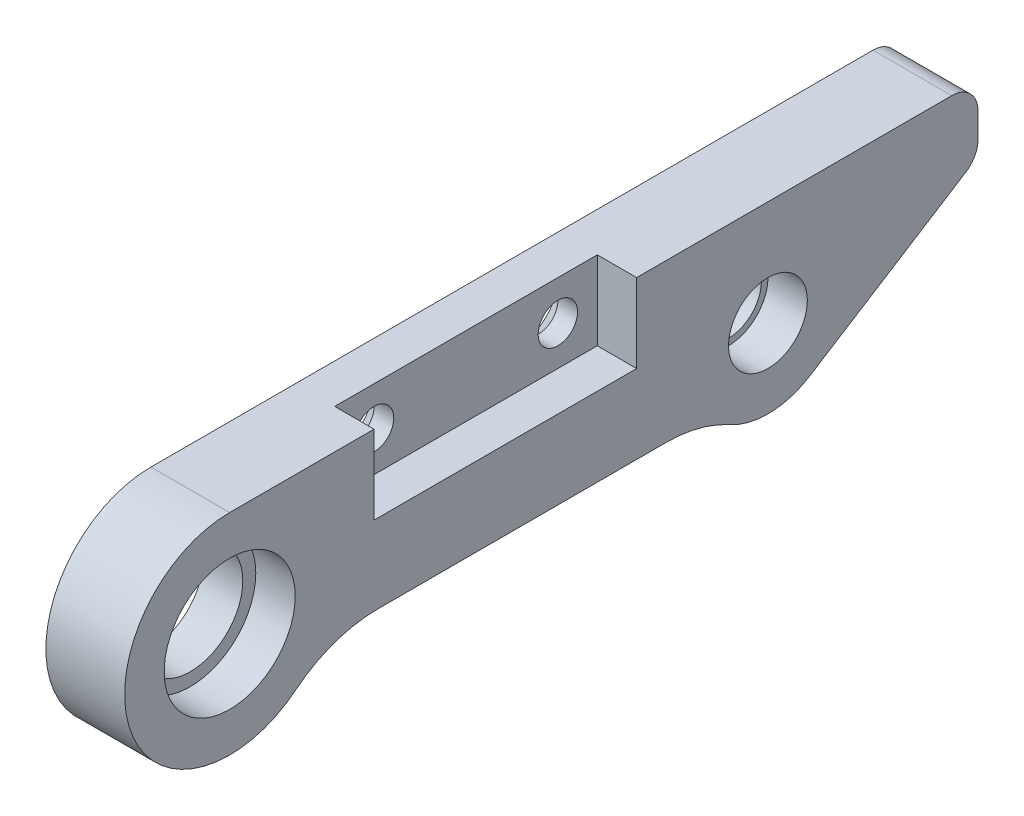
SolidWorks part; units mm, degrees
material "1060 Alloy"
ref_plane "Front Plane" through (0, 0, 0) normal (0, 0, 1) x (1, 0, 0)
ref_plane "Top Plane" through (0, 0, 0) normal (0, 1, 0) x (1, 0, 0)
ref_plane "Right Plane" through (0, 0, 0) normal (1, 0, 0) x (0, 0, -1)
sketch "Sketch27" plane through (0, 0, 0) normal (1, 0, 0) x (0, 0, -1)
  line L2 (9, 50) -> (66, 50)
  line L3 (9, 42) -> (30.9317, 42) construction
  line L4 (30.9317, 42) -> (30.9317, 54) construction
  line L6 (9, 34) -> (48.5644, 34)
  line L7 (30.9317, 54) -> (9, 42) construction
  line L8 (0, 0) -> (60, 0) construction
  line L9 (0, 0) -> (0, 58) construction
  line L10 (0, 58) -> (60, 58) construction
  line L11 (60, 0) -> (60, 58) construction
  line L12 (66, 50) -> (66, 45)
  line L13 (48.5644, 34) -> (66, 45)
  arc A0 (9, 50) -> (9, 34) centre (9, 42) ccw
  circle A1 centre (50, 42) radius 6 construction
  circle A3 centre (9, 42) radius 5.6 construction
  circle A5 centre (9, 42) radius 4
  circle A6 centre (50, 42) radius 2.5
  dimension "D9" = 12
  dimension "D10" = 5
  dimension "D12" = 8
  dimension "D13" = 8
  dimension "D14" = 5
  dimension "D6" = 16
  dimension "D16" = 11.2
  dimension "D1" = 60
  dimension "D2" = 58
  dimension "D3" = 42
  dimension "D4" = 9
  dimension "D5" = 50
  dimension "D7" = 42
  dimension "D8" = 12
  dimension "D17" = 25
extrude "Boss-Extrude1" add sketch "Sketch27" along normal blind 6
sketch "Sketch33" plane through (6, 0, 0) normal (1, 0, 0) x (0, 0, -1)
  circle A0 centre (9, 42) radius 4.99
  dimension "D1" = 9.98
extrude "Cut-Extrude2" cut sketch "Sketch33" against normal blind 3
sketch "Sketch34" plane through (6, 0, 0) normal (1, 0, 0) x (0, 0, -1)
  line L0 (20, 44) -> (40, 44)
  line L1 (20, 44) -> (20, 50)
  line L2 (40, 44) -> (40, 50)
  line L3 (20, 50) -> (40, 50)
  line L5 (9, 42) -> (43.3727, 42) construction
  circle A0 centre (50, 42) radius 2.5 construction
  dimension "D1" = 20
  dimension "D2" = 6
  dimension "D3" = 10
  dimension "D4" = 2
extrude "Cut-Extrude3" cut sketch "Sketch34" against normal blind 3
sketch "Sketch36" plane through (3, 0, 0) normal (1, 0, 0) x (0, 0, -1)
  line L0 (20, 50) -> (20, 44) construction
  line L2 (40, 44) -> (40, 50) construction
  line L3 (20, 44) -> (40, 44) construction
  circle A0 centre (23, 47) radius 1.5
  circle A1 centre (37, 47) radius 1.5
  dimension "D1" = 3
  dimension "D2" = 3
  dimension "D3" = 3
  dimension "D5" = 3
extrude "Cut-Extrude5" cut sketch "Sketch36" against normal up to next
fillet "Fillet3" radius 2 2 edges at (3, 50, -66) (3, 45, -66)
fillet "Fillet4" radius 10 1 edges at (3, 34, -48.5644)
sketch "Sketch37" plane through (6, 0, 0) normal (1, 0, 0) x (0, 0, -1)
  line L1 (9, 34) -> (45.6736, 34) construction
  line L2 (20.3137, 38) -> (42.254, 38)
  line L3 (51.0093, 35.5425) -> (65.0672, 44.4115) construction
  line L4 (9, 34) -> (53.2015, 34)
  line L5 (53.2015, 34) -> (53.2015, 36.9255)
  line L6 (20, 44) -> (40, 44) construction
  arc A0 (9, 34) -> (14.0283, 35.7778) centre (9, 42) ccw
  arc A1 (14.0283, 35.7778) -> (20.3137, 38) centre (20.3137, 28) cw
  arc A2 (42.254, 38) -> (47.0953, 36.75) centre (42.254, 28) cw
  arc A3 (47.0953, 36.75) -> (53.2015, 36.9255) centre (50, 42) ccw
  circle A4 centre (50, 42) radius 2.5 construction
  circle A5 centre (9, 42) radius 4.99 construction
  dimension "D2" = 10
  dimension "D1" = 6
extrude "Cut-Extrude6" cut sketch "Sketch37" against normal up to next
chamfer "Chamfer1" distance 1.5 angle 45 2 edges at (0, 47, -24.5) (0, 47, -38.5)
sketch "Sketch38" plane through (6, 0, 0) normal (1, 0, 0) x (0, 0, -1)
  circle A0 centre (50, 42) radius 3
  dimension "D1" = 6
extrude "Cut-Extrude7" cut sketch "Sketch38" against normal blind 3
